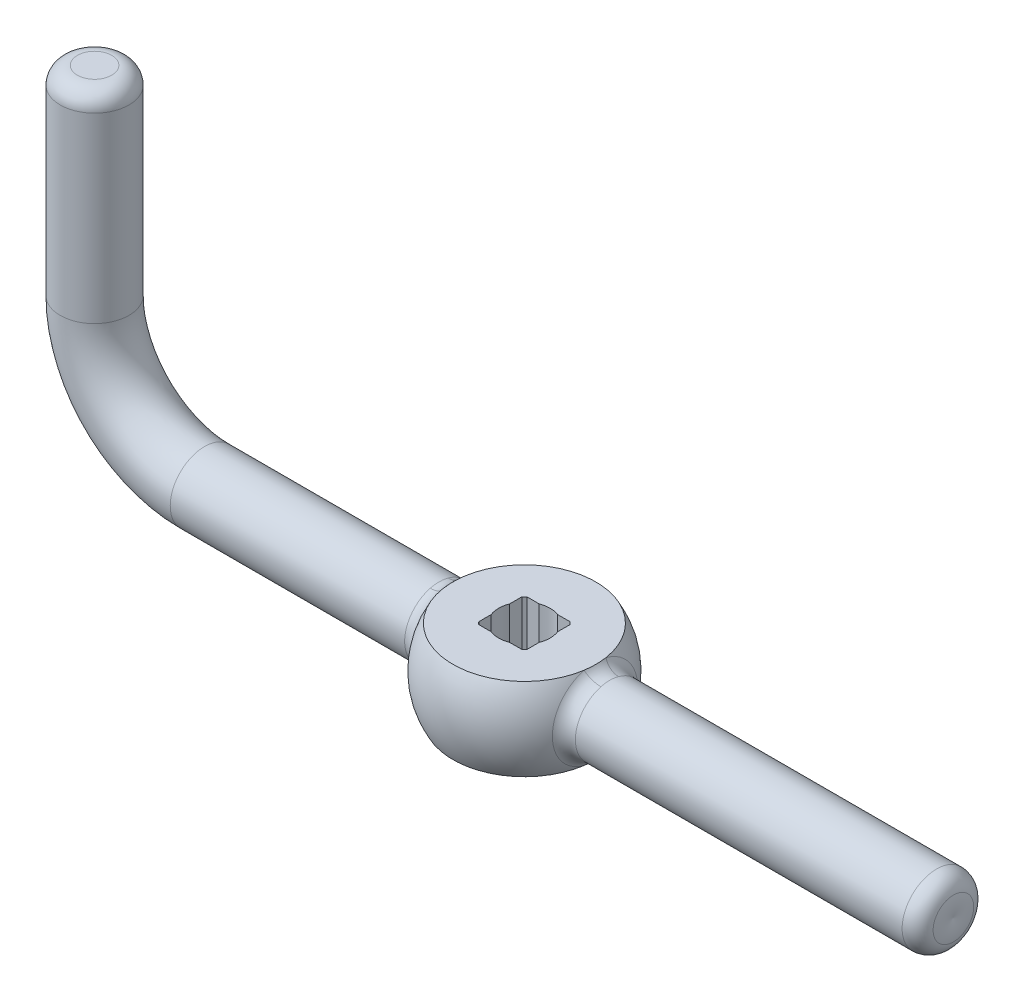
SolidWorks part; units mm, degrees
material "Алюминиевая бронза"
ref_plane "Спереди" through (0, 0, 0) normal (0, 0, 1) x (1, 0, 0)
ref_plane "Сверху" through (0, 0, 0) normal (0, 1, 0) x (1, 0, 0)
ref_plane "Справа" through (0, 0, 0) normal (1, 0, 0) x (0, 0, -1)
sketch "Эскиз1" plane through (0, 0, 0) normal (0, 0, 1) x (1, 0, 0)
  line L0 (-125, 90) -> (-125, 32)
  line L1 (-93, 0) -> (125, 0)
  arc A0 (-125, 32) -> (-93, 0) centre (-93, 32) ccw
  point P6 (0, 0)
  dimension "D1" = 32
  dimension "D2" = 90
  dimension "D3" = 250
  dimension "D4" = 125
ref_plane "Плоскость1" through (0, 90, 0) normal (0, 1, 0) x (1, 0, 0)
sketch "Эскиз2" plane through (0, 90, 0) normal (0, 1, 0) x (1, 0, 0)
  circle A0 centre (-125, 0) radius 10
  dimension "D1" = 20
sweep "По траектории1" add profiles "Эскиз2" path "Эскиз1"
sketch "Эскиз3" plane through (0, 0, 0) normal (0, 0, 1) x (1, 0, 0)
  line L0 (0, 20.3535) -> (0, -20.2704) construction
  line L1 (0, 12) -> (0, -12)
  line L2 (0, 12) -> (-20.7846, 12)
  line L3 (0, -12) -> (-20.7846, -12)
  arc A0 (-20.7846, 12) -> (-20.7846, -12) centre (0, 0) ccw
  dimension "D3" = 48
  dimension "D1" = 24
revolve "Повернуть1" add sketch "Эскиз3" angle 360 about L0
sketch "Эскиз6" plane through (0, 0, 0) normal (0, 0, 1) x (1, 0, 0)
  line L0 (-23.2387, 0) -> (276.6766, 0) construction
  line L1 (-93, -10) -> (-21.8174, -10) construction
  line L2 (125, 10) -> (21.8174, 10) construction
  line L4 (125, -10) -> (125, 10) construction
  line L5 (123.3346, 10) -> (253.9349, 10)
  line L6 (253.9349, 10) -> (253.9349, 0)
  line L7 (253.9349, 0) -> (124.5865, 0)
  arc A0 (123.3346, 10) -> (124.5865, 0) centre (111, 3.3774) cw
  dimension "D2" = 14
  dimension "D1" = 10
revolve "Вырез-Повернуть1" cut sketch "Эскиз6" angle 360 about L0
fillet "Скругление1" radius 5 4 edges at (-21.8174, 0, -10) (21.8174, 0, 10) (123.3346, 0, 10) (-125, 90, 10)
sketch "Эскиз7" plane through (0, 0, 0) normal (0, 1, 0) x (1, 0, 0)
  line L1 (-7, -7) -> (7, -7)
  line L2 (-7, -7) -> (-7, 7)
  line L3 (-7, 7) -> (7, 7)
  line L4 (7, -7) -> (7, 7)
  line L5 (-7, -7) -> (7, 7) construction
  line L6 (-7, 7) -> (7, -7) construction
  circle A0 centre (0, 0) radius 7.5
  circle A1 centre (0, 0) radius 9.4
  dimension "D2" = 18.8
  dimension "D3" = 14
  dimension "D1" = 15
extrude "Вырез-Вытянуть1" cut sketch "Эскиз7" against normal through all both and the other way through all contours L4 A1 L3 A0 | L1 A0 L4 L3 L2 | L3 A0 | L3 A1 L2 A0 | L2 A0 | L2 A1 L1 A0 | L1 A0 | L1 A1 L4 A0 | L4 A0 region at (-5.7384, 0, 5.7384) region at (0, 0, 0) region at (0, 0, 7.2006) region at (5.7384, 0, 5.7384) region at (-7.2006, 0, 0) region at (-5.7384, 0, -5.7384) region at (7.2006, 0, 0) region at (0, 0, -7.2006) region at (5.7384, 0, -5.7384)
